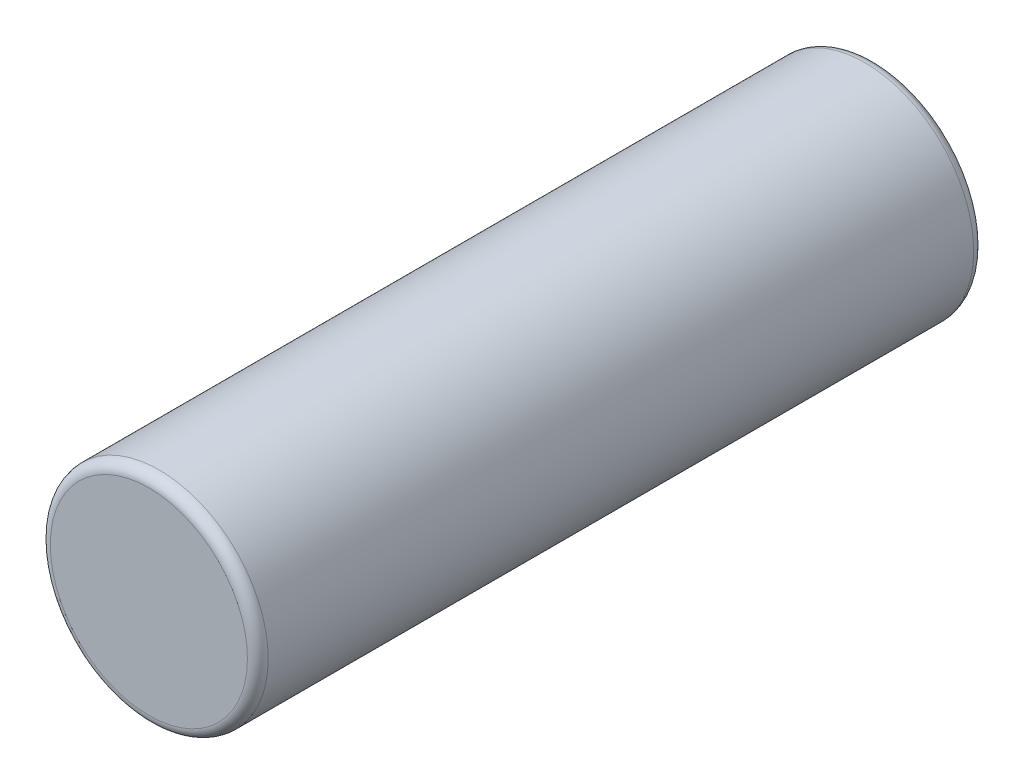
SolidWorks part; units mm, degrees
material "Copper"
ref_plane "Front Plane" through (0, 0, 0) normal (0, 0, 1) x (1, 0, 0)
ref_plane "Top Plane" through (0, 0, 0) normal (0, 1, 0) x (1, 0, 0)
ref_plane "Right Plane" through (0, 0, 0) normal (1, 0, 0) x (0, 0, -1)
sketch "Sketch1" plane through (0, 0, 0) normal (0, 0, 1) x (1, 0, 0)
  circle A4 centre (0, 0) radius 10.5
  dimension "D1" = 21
extrude "Boss-Extrude1" add sketch "Sketch1" along normal blind 70 contours A4 region at (0, 0, 0)
fillet "Fillet1" radius 1 2 edges at (10.5, 0, 0) (10.5, 0, 70)
